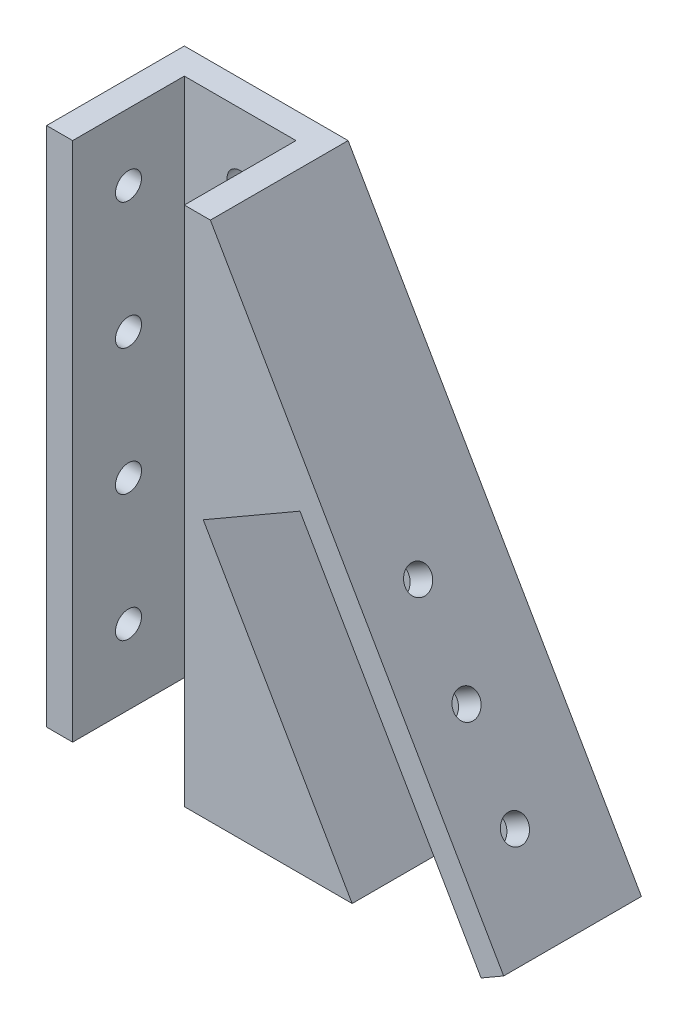
SolidWorks part; units mm, degrees
ref_plane "Front Plane" through (0, 0, 0) normal (0, 0, 1) x (1, 0, 0)
ref_plane "Top Plane" through (0, 0, 0) normal (0, 1, 0) x (1, 0, 0)
ref_plane "Right Plane" through (0, 0, 0) normal (1, 0, 0) x (0, 0, -1)
sketch "Sketch1" plane through (0, 0, 0) normal (0, 0, 1) x (1, 0, 0)
  line L0 (7.855, 37.4696) -> (48.2584, -32.5112)
  line L1 (-14.145, 37.4696) -> (7.855, 37.4696)
  line L2 (-14.145, 37.4696) -> (-14.145, -32.5112)
  line L3 (-14.145, -32.5112) -> (7.855, -32.5112)
  line L4 (7.855, 37.4696) -> (7.855, -32.5112) construction
  line L5 (48.2584, -32.5112) -> (7.855, -32.5112)
  line L6 (22.855, -32.5112) -> (7.855, -6.5304) construction
  line L7 (7.855, -6.5304) -> (44.3314, 14.5292) construction
  dimension "D1" = 22
  dimension "D2" = 30
  dimension "D3" = 22
  dimension "D4" = 30
extrude "Boss-Extrude1" add sketch "Sketch1" along normal blind 18.5
sketch "Sketch2" plane through (0, 0, 18.5) normal (0, 0, 1) x (1, 0, 0)
  line L0 (7.855, 37.4696) -> (-14.145, 37.4696) construction
  line L1 (-14.145, -32.5112) -> (48.2584, -32.5112) construction
  line L2 (-10.645, 37.4696) -> (4.355, 37.4696)
  line L3 (-10.645, 37.4696) -> (-10.645, -32.5112)
  line L4 (-10.645, -32.5112) -> (4.355, -32.5112)
  line L5 (4.355, 37.4696) -> (4.355, -32.5112)
  line L6 (-14.145, 37.4696) -> (-14.145, -32.5112) construction
  line L7 (44.2169, -32.5112) -> (19.8868, 9.6298)
  line L8 (19.8868, 9.6298) -> (6.8964, 2.1298)
  line L9 (6.8964, 2.1298) -> (26.8964, -32.5112)
  line L10 (26.8964, -32.5112) -> (44.2169, -32.5112)
  line L11 (48.2584, -32.5112) -> (7.855, 37.4696) construction
  dimension "D1" = 15
  dimension "D2" = 3.5
  dimension "D3" = 3.5
  dimension "D4" = 15
  dimension "D5" = 40
extrude "Cut-Extrude1" cut sketch "Sketch2" against normal offset from surface (15 mm away) 3.5 up to face at (6.9558, 2.4792, 0)
sketch "Sketch3" plane through (22.116, 12.7687, 0) normal (0.866, 0.5, 0) x (0, 0, -1)
  line L0 (-11, 30.2721) -> (-11, -52.2847) construction
  line L1 (-3.5, 30.2721) -> (-18.5, 30.2721) construction
  line L2 (-18.5, -52.2847) -> (0, -52.2847) construction
  circle A0 centre (-11, -38.2847) radius 1.75
  circle A1 centre (-11, -25.2847) radius 1.75
  circle A2 centre (-11, -12.2847) radius 1.75
  dimension "D1" = 3.5
  dimension "D2" = 14
  dimension "D4" = 13
  dimension "D3" = 13
extrude "Cut-Extrude2" cut sketch "Sketch3" against normal blind 3.5
sketch "Sketch4" plane through (0, 0, 0) normal (0, 0, -1) x (-1, 0, 0)
  line L0 (3.145, 37.4696) -> (3.145, -32.5112) construction
  line L1 (-7.855, 37.4696) -> (14.145, 37.4696) construction
  line L2 (14.145, -32.5112) -> (-48.2584, -32.5112) construction
  line L3 (-13.3916, 5.8798) -> (-35.5567, -32.5112) construction
  line L4 (-6.8964, 2.1298) -> (-19.8868, 9.6298) construction
  circle A0 centre (-30.5567, -23.851) radius 1.75
  circle A1 centre (-24.0567, -12.5926) radius 1.75
  circle A2 centre (-17.5567, -1.3343) radius 1.75
  circle A3 centre (3.145, -5.5112) radius 1.75
  circle A4 centre (3.145, 11.4888) radius 1.75
  circle A5 centre (3.145, 28.4888) radius 1.75
  circle A6 centre (3.145, -22.5112) radius 1.75
  dimension "D1" = 10
  dimension "D2" = 13
  dimension "D3" = 13
  dimension "D4" = 3.5
  dimension "D5" = 4
  dimension "D6" = 10
extrude "Cut-Extrude3" cut sketch "Sketch4" against normal blind 4
sketch "Sketch5" plane through (-14.145, 0, 0) normal (-1, 0, 0) x (0, 0, 1)
  line L0 (11, 37.4696) -> (11, -32.5112) construction
  line L1 (18.5, 37.4696) -> (0, 37.4696) construction
  line L2 (18.5, -32.5112) -> (0, -32.5112) construction
  line L3 (18.5, 37.4696) -> (18.5, -32.5112) construction
  circle A0 centre (11, -22.5112) radius 1.75
  circle A1 centre (11, -5.5112) radius 1.75
  circle A2 centre (11, 11.4888) radius 1.75
  circle A3 centre (11, 28.4888) radius 1.75
  dimension "D2" = 3.5
  dimension "D3" = 10
  dimension "D1" = 7.5
  dimension "D4" = 4
extrude "Cut-Extrude4" cut sketch "Sketch5" against normal blind 4
sketch "Sketch6" plane through (0, 0, 18.5) normal (0, 0, 1) x (1, 0, 0)
  line L0 (44.2169, -32.5112) -> (47.248, -30.7612)
  line L1 (48.2584, -32.5112) -> (7.855, 37.4696) construction
  line L2 (47.248, -30.7612) -> (48.2584, -32.5112)
  line L3 (48.2584, -32.5112) -> (44.2169, -32.5112)
extrude "Cut-Extrude5" cut sketch "Sketch6" against normal blind 19
